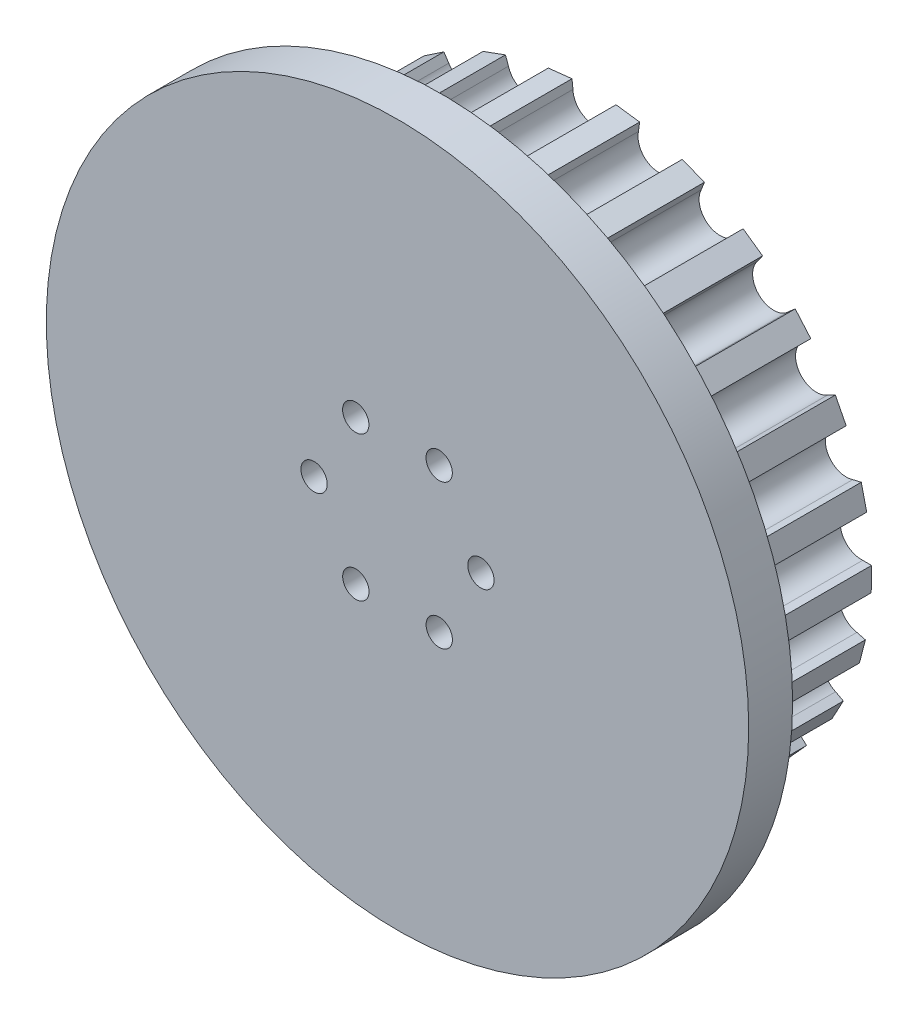
SolidWorks part; units mm, degrees
ref_plane "Front Plane" through (0, 0, 0) normal (0, 0, 1) x (1, 0, 0)
ref_plane "Top Plane" through (0, 0, 0) normal (0, 1, 0) x (1, 0, 0)
ref_plane "Right Plane" through (0, 0, 0) normal (1, 0, 0) x (0, 0, -1)
sketch "Sketch2" plane through (0, 0, 0) normal (0, 0, 1) x (1, 0, 0)
  line L0 (0.3691, 30.9978) -> (-7.0599, 30.1854) construction
  line L103 (-4.7156, 30.6392) -> (-4.8243, 31.6333)
  line L104 (-4.8243, 31.6333) -> (-2.1267, 31.9283)
  line L105 (-2.1267, 31.9283) -> (-2.018, 30.9342)
  line L106 (5.576, 31.5095) -> (5.4437, 30.5183)
  line L107 (2.7539, 30.8774) -> (2.8863, 31.8686)
  line L108 (2.8863, 31.8686) -> (5.576, 31.5095)
  line L109 (12.9547, 29.2595) -> (12.589, 28.3287)
  line L110 (10.0634, 29.3211) -> (10.4291, 30.2519)
  line L111 (10.4291, 30.2519) -> (12.9547, 29.2595)
  line L112 (19.5805, 25.309) -> (19.0027, 24.4928)
  line L113 (16.7879, 26.0608) -> (17.3658, 26.877)
  line L114 (17.3658, 26.877) -> (19.5805, 25.309)
  line L115 (25.0684, 19.8876) -> (24.312, 19.2334)
  line L116 (22.5369, 21.2859) -> (23.2932, 21.9401)
  line L117 (23.2932, 21.9401) -> (25.0684, 19.8876)
  line L118 (29.0994, 13.3104) -> (28.2084, 12.8563)
  line L119 (26.976, 15.2739) -> (27.867, 15.7281)
  line L120 (27.867, 15.7281) -> (29.0994, 13.3104)
  line L121 (31.4392, 5.9597) -> (30.4655, 5.732)
  line L122 (29.8475, 8.3743) -> (30.8212, 8.6021)
  line L123 (30.8212, 8.6021) -> (31.4392, 5.9597)
  line L124 (31.9519, -1.7373) -> (30.9519, -1.7254)
  line L125 (30.9843, 0.988) -> (31.9842, 0.9761)
  line L126 (31.9842, 0.9761) -> (31.9519, -1.7373)
  line L127 (30.6076, -9.3334) -> (29.6396, -9.0826)
  line L128 (30.3204, -6.4557) -> (31.2884, -6.7066)
  line L129 (31.2884, -6.7066) -> (30.6076, -9.3334)
  line L130 (27.4846, -16.3871) -> (26.6047, -15.9119)
  line L131 (27.8943, -13.5242) -> (28.7742, -13.9995)
  line L132 (28.7742, -13.9995) -> (27.4846, -16.3871)
  line L133 (22.7643, -22.4884) -> (22.0237, -21.8164)
  line L134 (23.8472, -19.8068) -> (24.5878, -20.4788)
  line L135 (24.5878, -20.4788) -> (22.7643, -22.4884)
  line L136 (16.7209, -27.2828) -> (16.1627, -26.4531)
  line L137 (18.4142, -24.9383) -> (18.9724, -25.768)
  line L138 (18.9724, -25.768) -> (16.7209, -27.2828)
  line L139 (9.7059, -30.4916) -> (9.3624, -29.5524)
  line L140 (11.911, -28.6204) -> (12.2544, -29.5596)
  line L141 (12.2544, -29.5596) -> (9.7059, -30.4916)
  line L142 (2.1267, -31.9283) -> (2.018, -30.9342)
  line L143 (4.7156, -30.6392) -> (4.8243, -31.6333)
  line L144 (4.8243, -31.6333) -> (2.1267, -31.9283)
  line L145 (-5.576, -31.5095) -> (-5.4437, -30.5183)
  line L146 (-2.7539, -30.8774) -> (-2.8863, -31.8686)
  line L147 (-2.8863, -31.8686) -> (-5.576, -31.5095)
  line L148 (-12.9547, -29.2595) -> (-12.589, -28.3287)
  line L149 (-10.0634, -29.3211) -> (-10.4291, -30.2519)
  line L150 (-10.4291, -30.2519) -> (-12.9547, -29.2595)
  line L151 (-19.5805, -25.309) -> (-19.0027, -24.4928)
  line L152 (-16.7879, -26.0608) -> (-17.3658, -26.877)
  line L153 (-17.3658, -26.877) -> (-19.5805, -25.309)
  line L154 (-25.0684, -19.8876) -> (-24.312, -19.2334)
  line L155 (-22.5369, -21.2859) -> (-23.2932, -21.9401)
  line L156 (-23.2932, -21.9401) -> (-25.0684, -19.8876)
  line L157 (-29.0994, -13.3104) -> (-28.2084, -12.8563)
  line L158 (-26.976, -15.2739) -> (-27.867, -15.7281)
  line L159 (-27.867, -15.7281) -> (-29.0994, -13.3104)
  line L160 (-31.4392, -5.9597) -> (-30.4655, -5.732)
  line L161 (-29.8475, -8.3743) -> (-30.8212, -8.6021)
  line L162 (-30.8212, -8.6021) -> (-31.4392, -5.9597)
  line L163 (-31.9519, 1.7373) -> (-30.9519, 1.7254)
  line L164 (-30.9843, -0.988) -> (-31.9842, -0.9761)
  line L165 (-31.9842, -0.9761) -> (-31.9519, 1.7373)
  line L166 (-30.6076, 9.3334) -> (-29.6396, 9.0826)
  line L167 (-30.3204, 6.4557) -> (-31.2884, 6.7066)
  line L168 (-31.2884, 6.7066) -> (-30.6076, 9.3334)
  line L169 (-27.4846, 16.3871) -> (-26.6047, 15.9119)
  line L170 (-27.8943, 13.5242) -> (-28.7742, 13.9995)
  line L171 (-28.7742, 13.9995) -> (-27.4846, 16.3871)
  line L172 (-22.7643, 22.4884) -> (-22.0237, 21.8164)
  line L173 (-23.8472, 19.8068) -> (-24.5878, 20.4788)
  line L174 (-24.5878, 20.4788) -> (-22.7643, 22.4884)
  line L175 (-16.7209, 27.2828) -> (-16.1627, 26.4531)
  line L176 (-18.4142, 24.9383) -> (-18.9724, 25.768)
  line L177 (-18.9724, 25.768) -> (-16.7209, 27.2828)
  line L178 (-9.7059, 30.4916) -> (-9.3624, 29.5524)
  line L179 (-11.911, 28.6204) -> (-12.2544, 29.5596)
  line L180 (-12.2544, 29.5596) -> (-9.7059, 30.4916)
  circle A0 centre (0, 0) radius 27.5
  circle A1 centre (0, 0) radius 31
  arc A103 (-4.7156, 30.6392) -> (-2.018, 30.9342) centre (0, 0) cw
  arc A104 (2.7539, 30.8774) -> (5.4437, 30.5183) centre (0, 0) cw
  arc A105 (10.0634, 29.3211) -> (12.589, 28.3287) centre (0, 0) cw
  arc A106 (16.7879, 26.0608) -> (19.0027, 24.4928) centre (0, 0) cw
  arc A107 (22.5369, 21.2859) -> (24.312, 19.2334) centre (0, 0) cw
  arc A108 (26.976, 15.2739) -> (28.2084, 12.8563) centre (0, 0) cw
  arc A109 (29.8475, 8.3743) -> (30.4655, 5.732) centre (0, 0) cw
  arc A110 (30.9843, 0.988) -> (30.9519, -1.7254) centre (0, 0) cw
  arc A111 (30.3204, -6.4557) -> (29.6396, -9.0826) centre (0, 0) cw
  arc A112 (27.8943, -13.5242) -> (26.6047, -15.9119) centre (0, 0) cw
  arc A113 (23.8472, -19.8068) -> (22.0237, -21.8164) centre (0, 0) cw
  arc A114 (18.4142, -24.9383) -> (16.1627, -26.4531) centre (0, 0) cw
  arc A115 (11.911, -28.6204) -> (9.3624, -29.5524) centre (0, 0) cw
  arc A116 (4.7156, -30.6392) -> (2.018, -30.9342) centre (0, 0) cw
  arc A117 (-2.7539, -30.8774) -> (-5.4437, -30.5183) centre (0, 0) cw
  arc A118 (-10.0634, -29.3211) -> (-12.589, -28.3287) centre (0, 0) cw
  arc A119 (-16.7879, -26.0608) -> (-19.0027, -24.4928) centre (0, 0) cw
  arc A120 (-22.5369, -21.2859) -> (-24.312, -19.2334) centre (0, 0) cw
  arc A121 (-26.976, -15.2739) -> (-28.2084, -12.8563) centre (0, 0) cw
  arc A122 (-29.8475, -8.3743) -> (-30.4655, -5.732) centre (0, 0) cw
  arc A123 (-30.9843, -0.988) -> (-30.9519, 1.7254) centre (0, 0) cw
  arc A124 (-30.3204, 6.4557) -> (-29.6396, 9.0826) centre (0, 0) cw
  arc A125 (-27.8943, 13.5242) -> (-26.6047, 15.9119) centre (0, 0) cw
  arc A126 (-23.8472, 19.8068) -> (-22.0237, 21.8164) centre (0, 0) cw
  arc A127 (-18.4142, 24.9383) -> (-16.1627, 26.4531) centre (0, 0) cw
  circle A128 centre (7.7766, 30.0087) radius 2.3879
  circle A129 centre (14.7322, 27.2757) radius 2.3879
  circle A130 centre (20.8316, 22.9575) radius 2.3879
  circle A131 centre (25.7203, 17.305) radius 2.3879
  circle A132 centre (29.1143, 10.6469) radius 2.3879
  circle A133 centre (30.8163, 3.37) radius 2.3879
  circle A134 centre (30.7273, -4.1027) radius 2.3879
  circle A135 centre (28.8526, -11.337) radius 2.3879
  circle A136 centre (25.301, -17.9125) radius 2.3879
  circle A137 centre (20.2791, -23.4469) radius 2.3879
  circle A138 centre (14.0786, -27.6187) radius 2.3879
  circle A139 centre (7.0599, -30.1854) radius 2.3879
  circle A140 centre (-0.3691, -30.9978) radius 2.3879
  circle A141 centre (-7.7766, -30.0087) radius 2.3879
  circle A142 centre (-14.7322, -27.2757) radius 2.3879
  circle A143 centre (-20.8316, -22.9575) radius 2.3879
  circle A144 centre (-25.7203, -17.305) radius 2.3879
  circle A145 centre (-29.1143, -10.6469) radius 2.3879
  circle A146 centre (-30.8163, -3.37) radius 2.3879
  circle A147 centre (-30.7273, 4.1027) radius 2.3879
  circle A148 centre (-28.8526, 11.337) radius 2.3879
  circle A149 centre (-25.301, 17.9125) radius 2.3879
  circle A150 centre (-20.2791, 23.4469) radius 2.3879
  circle A151 centre (-14.0786, 27.6187) radius 2.3879
  circle A152 centre (-7.0599, 30.1854) radius 2.3879
  circle A153 centre (0.3691, 30.9978) radius 2.3879
  arc A154 (-11.911, 28.6204) -> (-9.3624, 29.5524) centre (0, 0) cw
  point P64 (0, 0)
  point P79 (0, 0)
  point P164 (0, 0)
  point P176 (0, 0)
  point P178 (0, 0)
  point P185 (0, 0)
  point P269 (0, 0)
  point P363 (0, 0)
  dimension "D1" = 55
  dimension "D2" = 62
  dimension "D4" = 1
  dimension "D5" = 1
  dimension "D3" = 26
extrude "Boss-Extrude4" add sketch "Sketch2" against normal blind 17 contours A153 L0 A152 A1 A151 A150 A149 A148 A147 A146 A145 A144 A143 A142 A141 A140 A139 A138 A137 A136 A135 A134 A133 A132 A131 A130 A129 A128 | A1 L105 L104 L103 | L0 A153 A1 A152 | A1 L106 L108 L107 | A1 L109 L111 L110 | A1 L112 L114 L113 | A1 L115 L117 L116 | A1 L118 L120 L119 | A1 L121 L123 L122 | A1 L124 L126 L125 | A1 L127 L129 L128 | A1 L130 L132 L131 | A1 L133 L135 L134 | A1 L136 L138 L137 | A1 L139 L141 L140 | A1 L142 L144 L143 | A1 L148 L150 L149 | A1 L151 L153 L152 | A1 L154 L156 L155 | A1 L157 L159 L158 | A0 | A1 L145 L147 L146 | A1 L160 L162 L161 | A1 L163 L165 L164 | A1 L166 L168 L167 | A1 L169 L171 L170 | A1 L172 L174 L173 | A1 L175 L177 L176 | A1 L178 L180 L179 region at (0.4645, 27.7358, 0) region at (-3.3572, 30.6993, 0) region at (4.1663, 31.2032, 0) region at (-3.4222, 31.2936, 0) region at (11.5126, 29.2995, 0) region at (-10.8118, 29.5653, 0) region at (18.1899, 25.6929, 0) region at (-17.5731, 26.1187, 0) region at (23.8101, 20.5932, 0) region at (-23.313, 21.1542, 0) region at (28.0465, 14.2967, 0) region at (-27.6982, 14.9604, 0) region at (30.6529, 7.1693, 0) region at (-30.4735, 7.897, 0) region at (31.4779, -0.3748, 0) region at (-31.4779, 0.3748, 0) region at (-30.6529, -7.1693, 0) region at (30.4735, -7.897, 0) region at (-28.0465, -14.2967, 0) region at (27.6982, -14.9604, 0) region at (-23.8101, -20.5932, 0) region at (23.313, -21.1542, 0) region at (-18.1899, -25.6929, 0) region at (17.5731, -26.1187, 0) region at (-11.5126, -29.2995, 0) region at (10.8118, -29.5653, 0) region at (-4.1663, -31.2032, 0) region at (3.4222, -31.2936, 0) region at (0, 0, 0)
sketch "Sketch6" plane through (0, 0, 0) normal (0, 0, 1) x (1, 0, 0)
  circle A0 centre (0, 0) radius 40
  dimension "D1" = 80
extrude "Boss-Extrude5" add sketch "Sketch6" along normal blind 5
sketch "Sketch9" plane through (0, 0, -17) normal (0, 0, -1) x (-1, 0, 0)
  circle A0 centre (0, 0) radius 22.5
  dimension "D1" = 45
extrude "Cut-Extrude2" cut sketch "Sketch9" against normal blind 8.9145
sketch "Sketch10" plane through (0, 0, -8.0855) normal (0, 0, -1) x (-1, 0, 0)
  circle A0 centre (0, 0) radius 9.5 construction
  circle A1 centre (-4.7446, 8.2304) radius 1.5
  circle A2 centre (4.7554, 8.2241) radius 1.5
  circle A3 centre (9.5, -0.0063) radius 1.5
  circle A4 centre (4.7446, -8.2304) radius 1.5
  circle A5 centre (-4.7554, -8.2241) radius 1.5
  circle A6 centre (-9.5, 0.0063) radius 1.5
  point P18 (0, 0)
  dimension "D1" = 19
  dimension "D2" = 3
  dimension "D3" = 6
extrude "Cut-Extrude3" cut sketch "Sketch10" against normal through all contours A1 | A6 | A5 | A4 | A3 | A2 | A1 region at (4.7446, 8.2304, -8.0855) region at (-4.7554, 8.2241, -8.0855) region at (-9.5, -0.0063, -8.0855) region at (-4.7446, -8.2304, -8.0855) region at (4.7554, -8.2241, -8.0855) region at (9.5, 0.0063, -8.0855)
